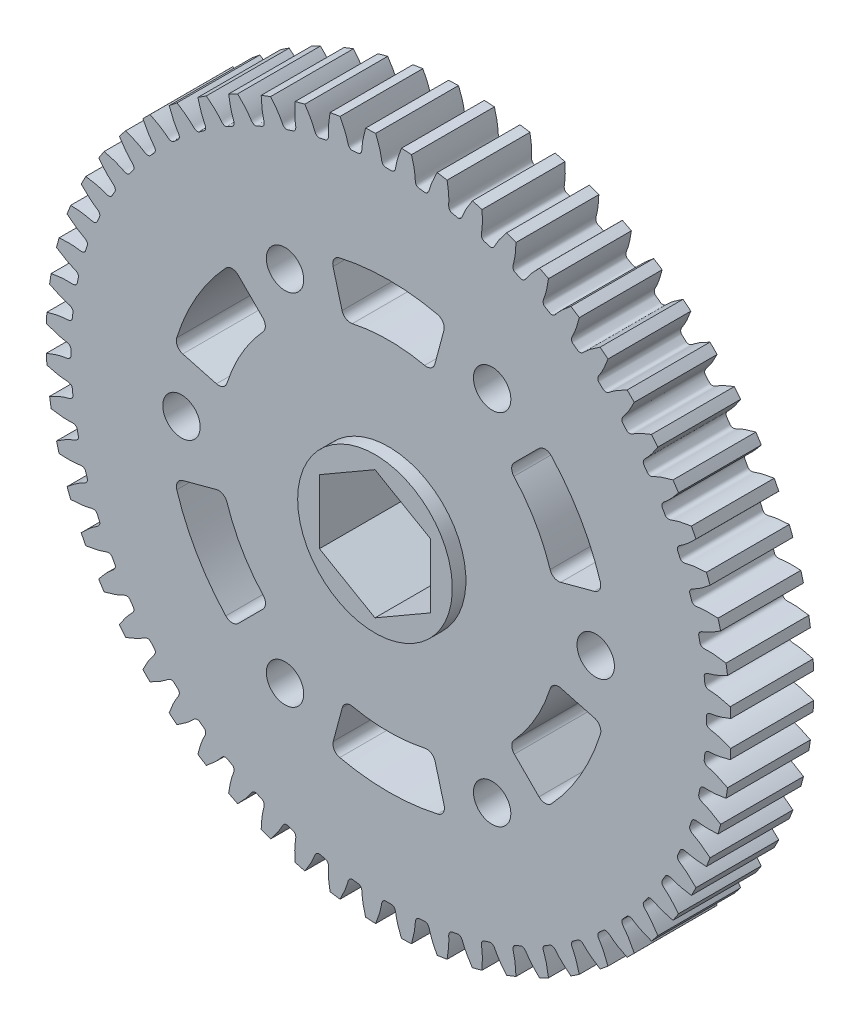
SolidWorks part; units mm, degrees
material "7075-T6 (SN)"
ref_plane "Front Plane" through (0, 0, 0) normal (0, 0, 1) x (1, 0, 0)
ref_plane "Top Plane" through (0, 0, 0) normal (0, 1, 0) x (1, 0, 0)
ref_plane "Right Plane" through (0, 0, 0) normal (1, 0, 0) x (0, 0, -1)
ref_plane "Plane1" through (0, 0, 4.7625) normal (0, 0, 1) x (1, 0, 0)
sketch "Sketch1" plane through (0, 0, 4.7625) normal (0, 0, 1) x (1, 0, 0)
  arc A0 (39.3421, 1.4811) -> (39.2814, 2.6394) centre (0, 0) ccw
  arc A1 (38.9718, 5.5854) -> (38.7904, 6.7309) centre (0, 0) ccw
  arc A2 (38.1745, 9.6285) -> (37.8743, 10.7487) centre (0, 0) ccw
  arc A3 (36.9589, 13.566) -> (36.5433, 14.6488) centre (0, 0) ccw
  arc A4 (35.3384, 17.355) -> (34.8118, 18.3884) centre (0, 0) ccw
  arc A5 (33.3307, 20.9538) -> (32.699, 21.9265) centre (0, 0) ccw
  arc A6 (30.9579, 24.323) -> (30.228, 25.2243) centre (0, 0) ccw
  arc A7 (28.2458, 27.4257) -> (27.4257, 28.2458) centre (0, 0) ccw
  arc A8 (25.2243, 30.228) -> (24.323, 30.9579) centre (0, 0) ccw
  arc A9 (21.9265, 32.699) -> (20.9538, 33.3307) centre (0, 0) ccw
  arc A10 (18.3884, 34.8118) -> (17.355, 35.3384) centre (0, 0) ccw
  arc A11 (14.6488, 36.5433) -> (13.566, 36.9589) centre (0, 0) ccw
  arc A12 (10.7487, 37.8743) -> (9.6285, 38.1745) centre (0, 0) ccw
  arc A13 (6.7309, 38.7904) -> (5.5854, 38.9718) centre (0, 0) ccw
  arc A14 (2.6394, 39.2814) -> (1.4811, 39.3421) centre (0, 0) ccw
  arc A15 (-1.4811, 39.3421) -> (-2.6394, 39.2814) centre (0, 0) ccw
  arc A16 (-5.5854, 38.9718) -> (-6.7309, 38.7904) centre (0, 0) ccw
  arc A17 (-9.6285, 38.1745) -> (-10.7487, 37.8743) centre (0, 0) ccw
  arc A18 (-13.566, 36.9589) -> (-14.6488, 36.5433) centre (0, 0) ccw
  arc A19 (-17.355, 35.3384) -> (-18.3884, 34.8118) centre (0, 0) ccw
  arc A20 (-20.9538, 33.3307) -> (-21.9265, 32.699) centre (0, 0) ccw
  arc A21 (-24.323, 30.9579) -> (-25.2243, 30.228) centre (0, 0) ccw
  arc A22 (-27.4257, 28.2458) -> (-28.2458, 27.4257) centre (0, 0) ccw
  arc A23 (-30.228, 25.2243) -> (-30.9579, 24.323) centre (0, 0) ccw
  arc A24 (-32.699, 21.9265) -> (-33.3307, 20.9538) centre (0, 0) ccw
  arc A25 (-34.8118, 18.3884) -> (-35.3384, 17.355) centre (0, 0) ccw
  arc A26 (-36.5433, 14.6488) -> (-36.9589, 13.566) centre (0, 0) ccw
  arc A27 (-37.8743, 10.7487) -> (-38.1745, 9.6285) centre (0, 0) ccw
  arc A28 (-38.7904, 6.7309) -> (-38.9718, 5.5854) centre (0, 0) ccw
  arc A29 (-39.2814, 2.6394) -> (-39.3421, 1.4811) centre (0, 0) ccw
  arc A30 (-39.3421, -1.4811) -> (-39.2814, -2.6394) centre (0, 0) ccw
  arc A31 (-38.9718, -5.5854) -> (-38.7904, -6.7309) centre (0, 0) ccw
  arc A32 (-38.1745, -9.6285) -> (-37.8743, -10.7487) centre (0, 0) ccw
  arc A33 (-36.9589, -13.566) -> (-36.5433, -14.6488) centre (0, 0) ccw
  arc A34 (-35.3384, -17.355) -> (-34.8118, -18.3884) centre (0, 0) ccw
  arc A35 (-33.3307, -20.9538) -> (-32.699, -21.9265) centre (0, 0) ccw
  arc A36 (-30.9579, -24.323) -> (-30.228, -25.2243) centre (0, 0) ccw
  arc A37 (-28.2458, -27.4257) -> (-27.4257, -28.2458) centre (0, 0) ccw
  arc A38 (-25.2243, -30.228) -> (-24.323, -30.9579) centre (0, 0) ccw
  arc A39 (-21.9265, -32.699) -> (-20.9538, -33.3307) centre (0, 0) ccw
  arc A40 (-18.3884, -34.8118) -> (-17.355, -35.3384) centre (0, 0) ccw
  arc A41 (-14.6488, -36.5433) -> (-13.566, -36.9589) centre (0, 0) ccw
  arc A42 (-10.7487, -37.8743) -> (-9.6285, -38.1745) centre (0, 0) ccw
  arc A43 (-6.7309, -38.7904) -> (-5.5854, -38.9718) centre (0, 0) ccw
  arc A44 (-2.6394, -39.2814) -> (-1.4811, -39.3421) centre (0, 0) ccw
  arc A45 (1.4811, -39.3421) -> (2.6394, -39.2814) centre (0, 0) ccw
  arc A46 (5.5854, -38.9718) -> (6.7309, -38.7904) centre (0, 0) ccw
  arc A47 (9.6285, -38.1745) -> (10.7487, -37.8743) centre (0, 0) ccw
  arc A48 (13.566, -36.9589) -> (14.6488, -36.5433) centre (0, 0) ccw
  arc A49 (17.355, -35.3384) -> (18.3884, -34.8118) centre (0, 0) ccw
  arc A50 (20.9538, -33.3307) -> (21.9265, -32.699) centre (0, 0) ccw
  arc A51 (24.323, -30.9579) -> (25.2243, -30.228) centre (0, 0) ccw
  arc A52 (27.4257, -28.2458) -> (28.2458, -27.4257) centre (0, 0) ccw
  arc A53 (30.228, -25.2243) -> (30.9579, -24.323) centre (0, 0) ccw
  arc A54 (32.699, -21.9265) -> (33.3307, -20.9538) centre (0, 0) ccw
  arc A55 (34.8118, -18.3884) -> (35.3384, -17.355) centre (0, 0) ccw
  arc A56 (36.5433, -14.6488) -> (36.9589, -13.566) centre (0, 0) ccw
  arc A57 (37.8743, -10.7487) -> (38.1745, -9.6285) centre (0, 0) ccw
  arc A58 (38.7904, -6.7309) -> (38.9718, -5.5854) centre (0, 0) ccw
  arc A59 (39.2814, -2.6394) -> (39.3421, -1.4811) centre (0, 0) ccw
  spline S0 degree 3 number of poles 79 (39.3421, 1.4811) -> (39.3421, -1.4811)
  spline S1 degree 3 number of poles 79 (38.9718, 5.5854) -> (39.2814, 2.6394)
  spline S2 degree 3 number of poles 79 (38.1745, 9.6285) -> (38.7904, 6.7309)
  spline S3 degree 3 number of poles 79 (36.9589, 13.566) -> (37.8743, 10.7487)
  spline S4 degree 3 number of poles 79 (35.3384, 17.355) -> (36.5433, 14.6488)
  spline S5 degree 3 number of poles 79 (33.3307, 20.9538) -> (34.8118, 18.3884)
  spline S6 degree 3 number of poles 79 (30.9579, 24.323) -> (32.699, 21.9265)
  spline S7 degree 3 number of poles 79 (28.2458, 27.4257) -> (30.228, 25.2243)
  spline S8 degree 3 number of poles 79 (25.2243, 30.228) -> (27.4257, 28.2458)
  spline S9 degree 3 number of poles 79 (21.9265, 32.699) -> (24.323, 30.9579)
  spline S10 degree 3 number of poles 79 (18.3884, 34.8118) -> (20.9538, 33.3307)
  spline S11 degree 3 number of poles 79 (14.6488, 36.5433) -> (17.355, 35.3384)
  spline S12 degree 3 number of poles 79 (10.7487, 37.8743) -> (13.566, 36.9589)
  spline S13 degree 3 number of poles 79 (6.7309, 38.7904) -> (9.6285, 38.1745)
  spline S14 degree 3 number of poles 79 (2.6394, 39.2814) -> (5.5854, 38.9718)
  spline S15 degree 3 number of poles 79 (-1.4811, 39.3421) -> (1.4811, 39.3421)
  spline S16 degree 3 number of poles 79 (-5.5854, 38.9718) -> (-2.6394, 39.2814)
  spline S17 degree 3 number of poles 79 (-9.6285, 38.1745) -> (-6.7309, 38.7904)
  spline S18 degree 3 number of poles 79 (-13.566, 36.9589) -> (-10.7487, 37.8743)
  spline S19 degree 3 number of poles 79 (-17.355, 35.3384) -> (-14.6488, 36.5433)
  spline S20 degree 3 number of poles 79 (-20.9538, 33.3307) -> (-18.3884, 34.8118)
  spline S21 degree 3 number of poles 79 (-24.323, 30.9579) -> (-21.9265, 32.699)
  spline S22 degree 3 number of poles 79 (-27.4257, 28.2458) -> (-25.2243, 30.228)
  spline S23 degree 3 number of poles 79 (-30.228, 25.2243) -> (-28.2458, 27.4257)
  spline S24 degree 3 number of poles 79 (-32.699, 21.9265) -> (-30.9579, 24.323)
  spline S25 degree 3 number of poles 79 (-34.8118, 18.3884) -> (-33.3307, 20.9538)
  spline S26 degree 3 number of poles 79 (-36.5433, 14.6488) -> (-35.3384, 17.355)
  spline S27 degree 3 number of poles 79 (-37.8743, 10.7487) -> (-36.9589, 13.566)
  spline S28 degree 3 number of poles 79 (-38.7904, 6.7309) -> (-38.1745, 9.6285)
  spline S29 degree 3 number of poles 79 (-39.2814, 2.6394) -> (-38.9718, 5.5854)
  spline S30 degree 3 number of poles 79 (-39.3421, -1.4811) -> (-39.3421, 1.4811)
  spline S31 degree 3 number of poles 79 (-38.9718, -5.5854) -> (-39.2814, -2.6394)
  spline S32 degree 3 number of poles 79 (-38.1745, -9.6285) -> (-38.7904, -6.7309)
  spline S33 degree 3 number of poles 79 (-36.9589, -13.566) -> (-37.8743, -10.7487)
  spline S34 degree 3 number of poles 79 (-35.3384, -17.355) -> (-36.5433, -14.6488)
  spline S35 degree 3 number of poles 79 (-33.3307, -20.9538) -> (-34.8118, -18.3884)
  spline S36 degree 3 number of poles 79 (-30.9579, -24.323) -> (-32.699, -21.9265)
  spline S37 degree 3 number of poles 79 (-28.2458, -27.4257) -> (-30.228, -25.2243)
  spline S38 degree 3 number of poles 79 (-25.2243, -30.228) -> (-27.4257, -28.2458)
  spline S39 degree 3 number of poles 79 (-21.9265, -32.699) -> (-24.323, -30.9579)
  spline S40 degree 3 number of poles 79 (-18.3884, -34.8118) -> (-20.9538, -33.3307)
  spline S41 degree 3 number of poles 79 (-14.6488, -36.5433) -> (-17.355, -35.3384)
  spline S42 degree 3 number of poles 79 (-10.7487, -37.8743) -> (-13.566, -36.9589)
  spline S43 degree 3 number of poles 79 (-6.7309, -38.7904) -> (-9.6285, -38.1745)
  spline S44 degree 3 number of poles 79 (-2.6394, -39.2814) -> (-5.5854, -38.9718)
  spline S45 degree 3 number of poles 79 (1.4811, -39.3421) -> (-1.4811, -39.3421)
  spline S46 degree 3 number of poles 79 (5.5854, -38.9718) -> (2.6394, -39.2814)
  spline S47 degree 3 number of poles 79 (9.6285, -38.1745) -> (6.7309, -38.7904)
  spline S48 degree 3 number of poles 79 (13.566, -36.9589) -> (10.7487, -37.8743)
  spline S49 degree 3 number of poles 79 (17.355, -35.3384) -> (14.6488, -36.5433)
  spline S50 degree 3 number of poles 79 (20.9538, -33.3307) -> (18.3884, -34.8118)
  spline S51 degree 3 number of poles 79 (24.323, -30.9579) -> (21.9265, -32.699)
  spline S52 degree 3 number of poles 79 (27.4257, -28.2458) -> (25.2243, -30.228)
  spline S53 degree 3 number of poles 79 (30.228, -25.2243) -> (28.2458, -27.4257)
  spline S54 degree 3 number of poles 79 (32.699, -21.9265) -> (30.9579, -24.323)
  spline S55 degree 3 number of poles 79 (34.8118, -18.3884) -> (33.3307, -20.9538)
  spline S56 degree 3 number of poles 79 (36.5433, -14.6488) -> (35.3384, -17.355)
  spline S57 degree 3 number of poles 79 (37.8743, -10.7487) -> (36.9589, -13.566)
  spline S58 degree 3 number of poles 79 (38.7904, -6.7309) -> (38.1745, -9.6285)
  spline S59 degree 3 number of poles 79 (39.2814, -2.6394) -> (38.9718, -5.5854)
extrude "Boss-Extrude1" add sketch "Sketch1" against normal blind 9.525
sketch "Sketch2" plane through (0, 0, 4.7625) normal (0, 0, 1) x (1, 0, 0)
  circle A0 centre (0, 0) radius 8.89
extrude "Boss-Extrude2" add sketch "Sketch2" along normal blind 1.5621
sketch "Sketch3" plane through (0, 0, -4.7625) normal (0, 0, -1) x (-1, 0, 0)
  circle A0 centre (0, 0) radius 8.89
extrude "Boss-Extrude3" add sketch "Sketch3" along normal blind 1.5621
sketch "Sketch4" plane through (0, 0, -6.3246) normal (0, 0, -1) x (-1, 0, 0)
  line L0 (6.3881, 3.6882) -> (0, 7.3763)
  line L1 (0, 7.3763) -> (-6.3881, 3.6882)
  line L2 (-6.3881, 3.6882) -> (-6.3881, -3.6882)
  line L3 (-6.3881, -3.6882) -> (0, -7.3763)
  line L4 (0, -7.3763) -> (6.3881, -3.6882)
  line L5 (6.3881, -3.6882) -> (6.3881, 3.6882)
extrude "Cut-Extrude1" cut sketch "Sketch4" against normal through all
sketch "Sketch5" plane through (0, 0, 4.7625) normal (0, 0, 1) x (1, 0, 0)
  line L0 (13.7706, -13.8065) -> (18.0133, -18.0492)
  line L1 (24.6442, -6.5508) -> (18.8486, -4.9979)
  arc A0 (18.0133, -18.0492) -> (24.6442, -6.5508) centre (0, 0) ccw
  arc A1 (18.8486, -4.9979) -> (13.7706, -13.8065) centre (0, 0) cw
extrude "Cut-Extrude2" cut sketch "Sketch5" against normal through all
sketch "Sketch6" plane through (0, 0, 4.7625) normal (0, 0, 1) x (1, 0, 0)
  line L0 (-5.0715, -18.829) -> (-6.6244, -24.6245)
  line L1 (6.6489, -24.6179) -> (5.096, -18.8223)
  arc A0 (-6.6244, -24.6245) -> (6.6489, -24.6179) centre (0, 0) ccw
  arc A1 (5.096, -18.8223) -> (-5.0715, -18.829) centre (0, 0) cw
extrude "Cut-Extrude3" cut sketch "Sketch6" against normal through all
sketch "Sketch7" plane through (0, 0, 4.7625) normal (0, 0, 1) x (1, 0, 0)
  line L0 (-18.8421, -5.0224) -> (-24.6377, -6.5753)
  line L1 (-17.9953, -18.0671) -> (-13.7526, -13.8245)
  arc A0 (-24.6377, -6.5753) -> (-17.9953, -18.0671) centre (0, 0) ccw
  arc A1 (-13.7526, -13.8245) -> (-18.8421, -5.0224) centre (0, 0) cw
extrude "Cut-Extrude4" cut sketch "Sketch7" against normal through all
sketch "Sketch8" plane through (0, 0, 4.7625) normal (0, 0, 1) x (1, 0, 0)
  line L0 (-13.7706, 13.8065) -> (-18.0133, 18.0492)
  line L1 (-24.6442, 6.5508) -> (-18.8486, 4.9979)
  arc A0 (-18.0133, 18.0492) -> (-24.6442, 6.5508) centre (0, 0) ccw
  arc A1 (-18.8486, 4.9979) -> (-13.7706, 13.8065) centre (0, 0) cw
extrude "Cut-Extrude5" cut sketch "Sketch8" against normal through all
sketch "Sketch9" plane through (0, 0, 4.7625) normal (0, 0, 1) x (1, 0, 0)
  line L0 (5.0715, 18.829) -> (6.6244, 24.6245)
  line L1 (-6.6489, 24.6179) -> (-5.096, 18.8223)
  arc A0 (6.6244, 24.6245) -> (-6.6489, 24.6179) centre (0, 0) ccw
  arc A1 (-5.096, 18.8223) -> (5.0715, 18.829) centre (0, 0) cw
extrude "Cut-Extrude6" cut sketch "Sketch9" against normal through all
sketch "Sketch10" plane through (0, 0, -4.7625) normal (0, 0, -1) x (-1, 0, 0)
  line L0 (-24.6377, 6.5753) -> (-18.8421, 5.0224)
  line L1 (-13.7526, 13.8245) -> (-17.9953, 18.0671)
  arc A0 (-17.9953, 18.0671) -> (-24.6377, 6.5753) centre (0, 0) ccw
  arc A1 (-18.8421, 5.0224) -> (-13.7526, 13.8245) centre (0, 0) cw
extrude "Cut-Extrude7" cut sketch "Sketch10" against normal through all
hole_wizard "Ø4.3 (4.3) Diameter Hole1" positions "Sketch12" profile "Sketch11" hole size "Ø4.3" standard "ANSI Metric"
sketch "Sketch12" plane through (0, 0, -4.7625) normal (0, 0, -1) x (-1, 0, 0)
  point P0 (-11.9063, 20.6222)
  point P1 (11.9062, 20.6222)
  point P2 (23.8125, 0)
  point P3 (11.9063, -20.6222)
  point P4 (-11.9062, -20.6222)
  point P5 (-23.8125, 0)
sketch "Sketch11" plane through (11.9063, 20.6222, -4.7625) normal (1, 0, 0) x (0, 1, 0)
  line L0 (0, 0) -> (0, 11.0871)
  line L1 (0, 11.0871) -> (2.15, 11.0871)
  line L2 (2.15, 11.0871) -> (2.15, 0)
  line L5 (2.15, 0) -> (0, 0)
  line L11 (0, -6.35) -> (0, 107.95) construction
  dimension "Thru Hole Dia." = 4.3
  dimension "Thru Hole Depth" = 11.0871
fillet "Fillet1" radius 1 24 edges at (-13.7526, -13.8245, 0) (18.8486, -4.9979, 0) (5.096, -18.8223, 0) (18.8421, 5.0224, 0) (-18.8421, -5.0224, 0) (17.9953, 18.0671, 0) (-5.0715, -18.829, 0) (13.7526, 13.8245, 0) (13.7706, -13.8065, 0) (6.6244, 24.6245, 0) (-24.6377, -6.5753, 0) (5.0715, 18.829, 0) (-17.9953, -18.0671, 0) (-6.6489, 24.6179, 0) (-6.6244, -24.6245, 0) (-5.096, 18.8223, 0) (6.6489, -24.6179, 0) (-18.0133, 18.0492, 0) (18.0133, -18.0492, 0) (-13.7706, 13.8065, 0) (24.6442, -6.5508, 0) (-24.6442, 6.5508, 0) (24.6377, 6.5753, 0) (-18.8486, 4.9979, 0) tangent propagation no
